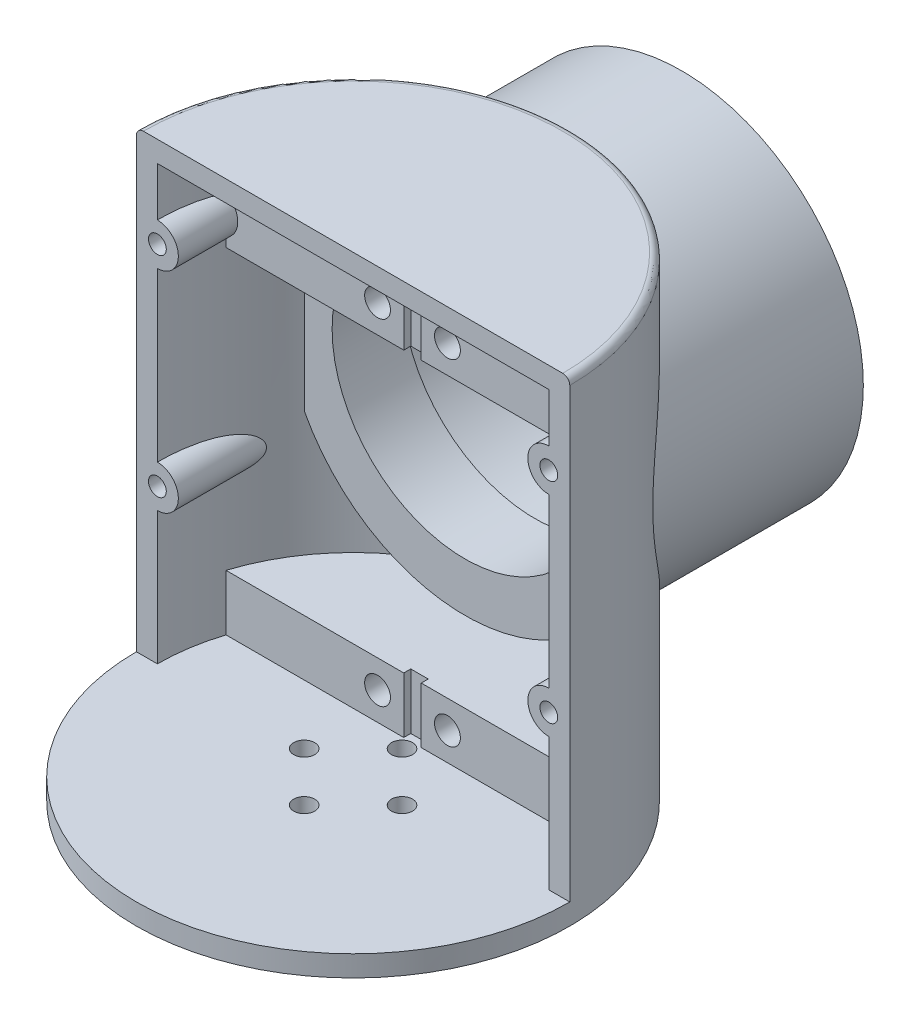
SolidWorks part; units mm, degrees
material "ABS"
ref_plane "Спереди" through (0, 0, 0) normal (0, 0, 1) x (1, 0, 0)
ref_plane "Сверху" through (0, 0, 0) normal (0, 1, 0) x (1, 0, 0)
ref_plane "Справа" through (0, 0, 0) normal (1, 0, 0) x (0, 0, -1)
sketch "Эскиз3" plane through (0, 0, 0) normal (1, 0, 0) x (0, 0, -1)
  line L0 (0, 68.2882) -> (0, 0) construction
  line L1 (0, 0) -> (31, 0)
  line L2 (31, 0) -> (31, 68)
  line L3 (31, 68) -> (0, 68)
  line L4 (0, 68) -> (0, 65)
  line L5 (0, 65) -> (28, 65)
  line L6 (28, 65) -> (28, 3)
  line L7 (28, 3) -> (0, 3)
  line L8 (0, 3) -> (0, 0)
  dimension "D1" = 62
  dimension "D2" = 68
  dimension "D3" = 3
  dimension "D4" = 3
  dimension "D5" = 3
revolve "Повернуть2" add sketch "Эскиз3" angle 360 about L0
sketch "Эскиз4" plane through (0, 68, 0) normal (0, 1, 0) x (1, 0, 0)
  line L0 (-31, 0) -> (31, 0)
  circle A0 centre (0, 0) radius 31 construction
  arc A1 (31, 0) -> (-31, 0) centre (0, 0) cw
extrude "Вырез-Вытянуть1" cut sketch "Эскиз4" against normal blind 65
sketch "Эскиз6" plane through (0, 0, 0) normal (0, -1, 0) x (1, 0, 0)
  circle A0 centre (7, 0) radius 1.5
  dimension "D1" = 3
  dimension "D2" = 7
extrude "Вырез-Вытянуть3" cut sketch "Эскиз6" against normal up to surface (3 mm away) up to face at (0, 3, 0.75)
pattern_circular "Круговой массив1" count 4 over 360 about axis through (0, 68.2882, 0) along (0, 1, 0) of "Вырез-Вытянуть3"
sketch "Эскиз7" plane through (0, 0, 0) normal (0, 0, 1) x (1, 0, 0)
  circle A0 centre (0, 41) radius 21
  circle A1 centre (0, 41) radius 26
  dimension "D1" = 52
  dimension "D2" = 42
  dimension "D3" = 41
extrude "Бобышка-Вытянуть1" add sketch "Эскиз7" against normal blind 31 from offset 16 offset against normal yes
sketch "Эскиз22" plane through (0, 0, -16) normal (0, 0, 1) x (1, 0, 0)
  line L0 (28, 3) -> (-28, 3) construction
  line L1 (-22.9783, 65) -> (22.9783, 65)
  line L2 (-22.9783, 65) -> (-22.9783, 51)
  line L3 (-22.9783, 51) -> (22.9783, 51)
  line L4 (22.9783, 65) -> (22.9783, 51)
  line L5 (-22.9783, 3) -> (22.9783, 3)
  line L6 (-28, 65) -> (-10, 65) construction
  line L7 (-22.9783, 28.8345) -> (-22.9783, 53.1655) construction
  line L8 (22.9783, 53.1655) -> (22.9783, 28.8345) construction
  line L9 (-22.9783, 3) -> (-22.9783, 11)
  line L10 (-22.9783, 11) -> (22.9783, 11)
  line L11 (22.9783, 3) -> (22.9783, 11)
  point P6 (0, 0)
  point P7 (0, 0)
  dimension "D1" = 14
  dimension "D2" = 8
extrude "Бобышка-Вытянуть7" add sketch "Эскиз22" against normal up to surface (7.5 mm away) from offset 7.5 up to face at (0.4346, 42.0206, -16.4737)
sketch "Эскиз8" plane through (0, 0, -47) normal (0, 0, -1) x (-1, 0, 0)
  circle A0 centre (0, 41) radius 21
  dimension "D1" = 42
  dimension "D2" = 41
extrude "Вырез-Вытянуть4" cut sketch "Эскиз8" against normal up to surface (31 mm away) up to face at (0, 36.1391, -16)
sketch "Эскиз11" plane through (0, 0, 0) normal (0, 0, 1) x (1, 0, 0)
  line L0 (-28, 65) -> (-28, 3) construction
  line L1 (28, 3) -> (28, 65) construction
  line L3 (-28, 25) -> (28, 25) construction
  line L4 (-28, 25) -> (-28, 55) construction
  line L5 (-28, 55) -> (28, 55) construction
  line L6 (28, 25) -> (28, 55) construction
  circle A0 centre (-28, 55) radius 3
  circle A1 centre (-28, 25) radius 3
  circle A2 centre (28, 25) radius 3
  circle A3 centre (28, 55) radius 3
  point P12 (0, 25)
  point P15 (28, 40)
  dimension "D1" = 6
  dimension "D2" = 6
  dimension "D3" = 6
  dimension "D4" = 6
  dimension "D5" = 30
  dimension "D6" = 40
extrude "Бобышка-Вытянуть3" add sketch "Эскиз11" against normal up to surface (12.6095 mm away) up to face at (0.2009, 31.4276, -13.2427)
hole_wizard "Сверло под метчик  спиральное M2.52" positions "Эскиз15" profile "Эскиз16" hole size "M2.5x0.45" standard "Ansi Metric"
sketch "Эскиз15" plane through (0, 0, 0) normal (0, 0, 1) x (1, 0, 0)
  point P0 (-28, 55)
  point P3 (28, 55)
  point P6 (28, 25)
  point P9 (-28, 25)
sketch "Эскиз16" plane through (-28, 55, 0) normal (1, 0, 0) x (0, -1, 0)
  line L0 (0, 0) -> (0, 5.7661)
  line L1 (0, 5.7661) -> (1.275, 5)
  line L2 (1.275, 5) -> (1.275, 0)
  line L5 (1.275, 0) -> (0, 0)
  line L10 (0, 5.7661) -> (-1.275, 5) construction
  line L11 (0, -6.35) -> (0, 107.95) construction
  dimension "Диаметр отверстия" = 2.55
  dimension "Глубина отверстия" = 5
  dimension "Угол заточки сверла" = 118
hole_wizard "Отверстие обработанное метчиком M2x0.41" positions "Эскиз18" profile "Эскиз19" tap size "M2x0.4" standard "HASCO Metric"
sketch "Эскиз18" plane through (0, 0, -47) normal (0, 0, -1) x (-1, 0, 0)
  line L2 (0, 41) -> (23, 41) construction
  line L4 (0, 41) -> (16.2635, 57.2635) construction
  circle A1 centre (0, 41) radius 23 construction
  point P0 (16.2635, 57.2635)
  dimension "D1" = 46
  dimension "D2" = 45
sketch "Эскиз19" plane through (-16.2635, 57.2635, -47) normal (1, 0, 0) x (0, 1, 0)
  line L0 (0, 0) -> (0, 10.4807)
  line L1 (0, 10.4807) -> (0.8, 10)
  line L2 (0.8, 10) -> (0.8, 0.225)
  line L3 (0.8, 0.225) -> (1.025, 0)
  line L5 (1.025, 0) -> (0, 0)
  line L6 (-0.8, 0.225) -> (-1.025, 0) construction
  line L10 (0, 10.4807) -> (-0.8, 10) construction
  line L11 (0, -6.35) -> (0, 107.95) construction
  dimension "Диаметр сверла" = 1.6
  dimension "Глубина сверла" = 10
  dimension "Диаметр передней зенковки" = 2.05
  dimension "Угол передней зенковки" = 90
  dimension "Угол заточки сверла" = 118
cosmetic thread "Отверстие резьбы1" parameters "D1"=8, "D2"=2
pattern_circular "Круговой массив2" count 8 over 360 about axis through (0, 41, -47) along (0, 0, 1) of "Отверстие обработанное метчиком M2x0.41"
ref_plane "Плоскость1" through (0, 0, -26) normal (0, 0, -1) x (-1, 0, 0)
sketch "Эскиз20" plane through (0, 0, -26) normal (0, 0, -1) x (-1, 0, 0)
  circle A0 centre (0, 41) radius 19
  circle A1 centre (0, 41) radius 26
  dimension "D1" = 38
  dimension "D2" = 52
extrude "Бобышка-Вытянуть6" add sketch "Эскиз20" against normal blind 10 contours A1 A0 region at (25.2646, 41, -26)
fillet "Скругление1" radius 1 1 edges at (0, 68, -31)
sketch "Эскиз23" plane through (-22.9783, 0, 0) normal (-1, 0, 0) x (0, 0, 1)
  line L1 (-16, 65) -> (-8.5, 65)
  line L2 (-16, 65) -> (-16, 51)
  line L3 (-16, 51) -> (-8.5, 51)
  line L4 (-8.5, 65) -> (-8.5, 51)
  line L5 (-16, 11) -> (-8.5, 11)
  line L6 (-16, 11) -> (-16, 3)
  line L7 (-16, 3) -> (-8.5, 3)
  line L8 (-8.5, 11) -> (-8.5, 3)
extrude "Бобышка-Вытянуть8" add sketch "Эскиз23" along normal up to next
mirror "Зеркальное отражение1" about plane through (0, 0, 0) normal (1, 0, 0) of "Бобышка-Вытянуть8"
sketch "Эскиз24" plane through (0, 0, -8.5) normal (0, 0, 1) x (1, 0, 0)
  line L0 (0, 51) -> (0, 66.3483) construction
  line L1 (-26.6786, 51) -> (26.6786, 51) construction
  line L2 (1.25, 51) -> (-1.25, 51)
  line L3 (-1.25, 51) -> (-1.25, 65)
  line L4 (-1.25, 65) -> (1.25, 65)
  line L5 (28, 65) -> (-28, 65) construction
  line L6 (1.25, 51) -> (1.25, 65)
  line L7 (1.25, 3) -> (-1.25, 3)
  line L8 (-26.6786, 3) -> (0, 3) construction
  line L9 (-1.25, 3) -> (-1.25, 11)
  line L10 (26.6786, 11) -> (-26.6786, 11) construction
  line L11 (-1.25, 11) -> (1.25, 11)
  line L12 (1.25, 3) -> (1.25, 11)
  point P14 (0, 65)
  point P15 (0, 0)
  point P23 (0, 11)
  point P24 (0, 3)
  dimension "D1" = 2.5
extrude "Вырез-Вытянуть5" cut sketch "Эскиз24" against normal blind 1
hole_wizard "Сверло под метчик  спиральное M3.51" positions "Эскиз25" profile "Эскиз26" hole size "M3.5x0.6" standard "Ansi Metric" end condition through all
sketch "Эскиз25" plane through (0, 0, -8.5) normal (0, 0, 1) x (1, 0, 0)
  line L0 (-26.6786, 51) -> (-1.25, 51) construction
  line L1 (-1.25, 51) -> (1.25, 51) construction
  line L3 (-1.25, 11) -> (-26.6786, 11) construction
  line L4 (1.25, 11) -> (-1.25, 11) construction
  point P0 (-5, 55)
  point P2 (5, 55)
  point P9 (0, 51)
  point P13 (-5, 7)
  point P15 (5, 7)
  point P22 (0, 0)
  point P25 (0, 11)
  dimension "D1" = 10
  dimension "D2" = 4
  dimension "D3" = 5
  dimension "D4" = 10
  dimension "D5" = 4
  dimension "D6" = 5
sketch "Эскиз26" plane through (-5, 55, -8.5) normal (1, 0, 0) x (0, -1, 0)
  line L0 (0, 0) -> (0, 38.5)
  line L1 (0, 38.5) -> (1.85, 38.5)
  line L2 (1.85, 38.5) -> (1.85, 0)
  line L5 (1.85, 0) -> (0, 0)
  line L11 (0, -6.35) -> (0, 107.95) construction
  dimension "Диаметр сквозного отверстия" = 3.7
  dimension "Глубина сквозного отверстия" = 38.5
